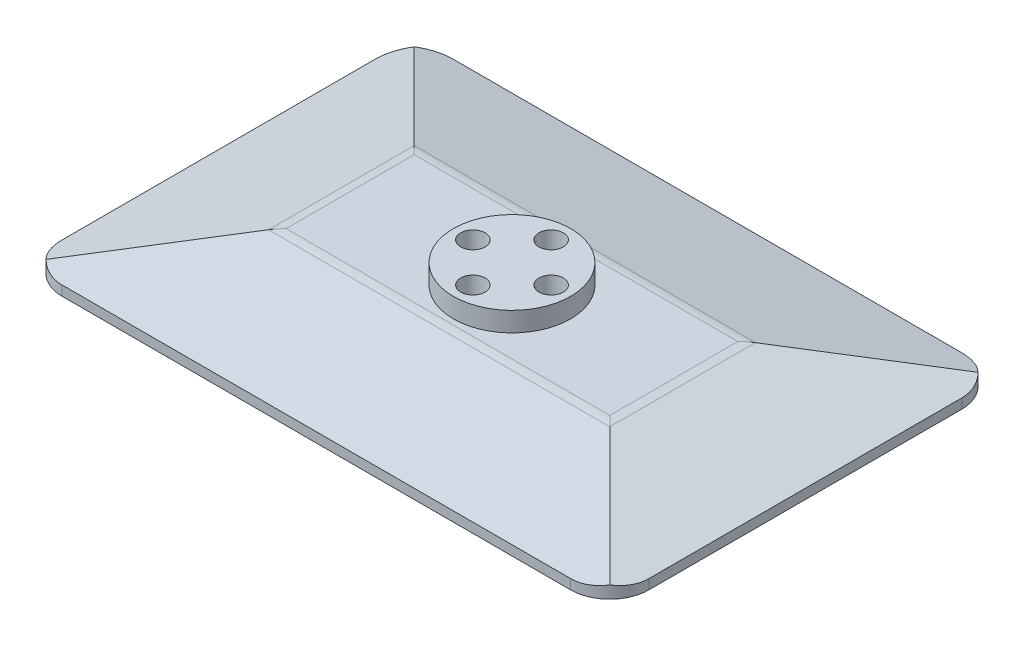
SolidWorks part; units mm, degrees
ref_plane "前视基准面" through (0, 0, 0) normal (0, 0, 1) x (1, 0, 0)
ref_plane "上视基准面" through (0, 0, 0) normal (0, 1, 0) x (1, 0, 0)
ref_plane "右视基准面" through (0, 0, 0) normal (1, 0, 0) x (0, 0, -1)
other "Configuration Table"
sketch "草图1" plane through (0, 0, 0) normal (0, 1, 0) x (1, 0, 0)
  line L0 (-48.5913, -10.2137) -> (-40.6154, -10.2137) construction
  line L1 (-33.5732, -10.2137) -> (-35.5732, -10.2137) construction
  line L2 (5.9754, 18.7871) -> (5.9754, 46.3845) construction
  line L3 (5.9754, 9.5066) -> (5.9754, -30.4934) construction
  line L5 (-24.0246, 9.7863) -> (35.9754, 9.7863)
  line L6 (-24.0246, 9.7863) -> (-24.0246, -30.2137)
  line L7 (-24.0246, -30.2137) -> (35.9754, -30.2137)
  line L8 (35.9754, 9.7863) -> (35.9754, -30.2137)
  line L9 (-24.0246, 9.7863) -> (35.9754, -30.2137) construction
  line L10 (-24.0246, -30.2137) -> (35.9754, 9.7863) construction
  point P8 (5.9754, -10.2137)
  dimension "D1" = 60
  dimension "D2" = 40
extrude "凸台-拉伸1" add sketch "草图1" along normal blind 1
sketch "草图2" plane through (0, 1, 0) normal (0, 1, 0) x (1, 0, 0)
  line L4 (35.9754, -30.2137) -> (35.9754, 9.7863)
  line L5 (35.9754, 9.7863) -> (-24.0246, 9.7863)
  line L6 (-24.0246, 9.7863) -> (-24.0246, -30.2137)
  line L7 (-24.0246, -30.2137) -> (35.9754, -30.2137)
  line L8 (35.9754, -30.2137) -> (35.9754, 9.7863)
  line L9 (35.9754, 9.7863) -> (-24.0246, 9.7863)
  line L10 (-24.0246, 9.7863) -> (-24.0246, -30.2137)
  line L11 (-24.0246, -30.2137) -> (35.9754, -30.2137)
  dimension "D1" = 0
extrude "凸台-拉伸2" add sketch "草图2" along normal blind 3 draft 77
fillet "圆角1" radius 4 4 edges at (-24.0246, 0.5, -9.7863) (35.9754, 0.5, -9.7863) (35.9754, 0.5, 30.2137) (-24.0246, 0.5, 30.2137)
sketch "草图3" plane through (0, 4, 0) normal (0, 1, 0) x (1, 0, 0)
  line L1 (5.9754, -12.2137) -> (5.9754, -8.2137) construction
  circle A0 centre (5.9754, -10.2137) radius 6
  dimension "D1" = 12
extrude "凸台-拉伸3" add sketch "草图3" along normal blind 2
fillet "圆角2" radius 4 4 edges at (22.9809, 4, 10.2137) (5.9754, 4, 3.2082) (-11.0302, 4, 10.2137) (5.9754, 4, 17.2193)
sketch "草图4" plane through (0, 6, 0) normal (0, 1, 0) x (1, 0, 0)
  line L0 (6.7345, -10.2137) -> (29.8962, -10.2137) construction
  line L2 (5.9754, 18.4249) -> (5.9754, 26.7292) construction
  line L3 (5.9754, -12.2137) -> (5.9754, -8.2137) construction
  circle A1 centre (1.9754, -10.2137) radius 1.25
  circle A2 centre (5.9754, -6.2137) radius 1.25
  circle A3 centre (9.9754, -10.2137) radius 1.25
  circle A4 centre (5.9754, -14.2137) radius 1.25
  point P17 (5.9754, -10.2137)
  dimension "D1" = 2.5
  dimension "D3" = 4
  dimension "D2" = 4
extrude "切除-拉伸1" cut sketch "草图4" against normal blind 3 draft 5
